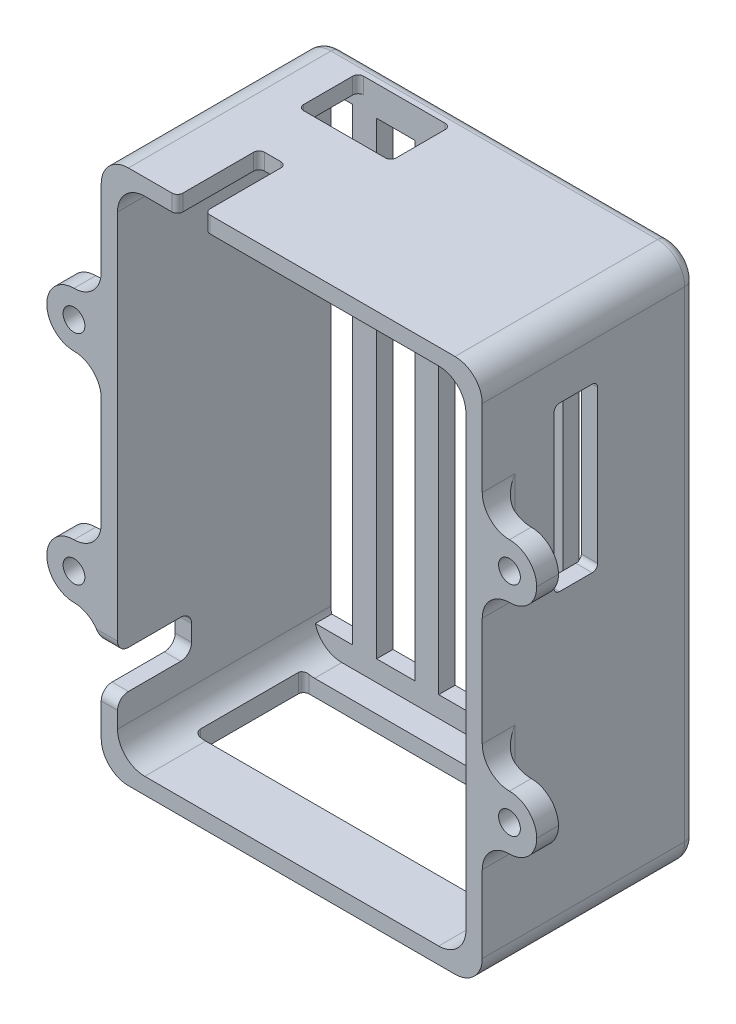
SolidWorks part; units mm, degrees
ref_plane "Front Plane" through (0, 0, 0) normal (0, 0, 1) x (1, 0, 0)
ref_plane "Top Plane" through (0, 0, 0) normal (0, 1, 0) x (1, 0, 0)
ref_plane "Right Plane" through (0, 0, 0) normal (1, 0, 0) x (0, 0, -1)
sketch "Sketch1" plane through (0, 0, 0) normal (0, 0, 1) x (1, 0, 0)
  line L1 (32, -46.145) -> (-32, -46.145)
  line L2 (32, -46.145) -> (32, 46.145)
  line L3 (32, 46.145) -> (-32, 46.145)
  line L4 (-32, -46.145) -> (-32, 46.145)
  line L5 (32, -46.145) -> (-32, 46.145) construction
  line L6 (32, 46.145) -> (-32, -46.145) construction
  line L12 (-25, -42.355) -> (-32, -42.355)
  line L13 (-25, -42.355) -> (-25, 43.645)
  line L14 (-25, 43.645) -> (-32, 43.645)
  line L15 (-32, -42.355) -> (-32, 43.645)
  line L16 (-25, -42.355) -> (-32, 43.645) construction
  line L17 (-25, 43.645) -> (-32, -42.355) construction
  line L57 (-13.6, -42.355) -> (-13.6, 43.645)
  line L58 (-13.6, -42.355) -> (-20.6, -42.355)
  line L59 (-20.6, -42.355) -> (-20.6, 43.645)
  line L60 (-13.6, 43.645) -> (-20.6, 43.645)
  line L61 (-2.2, -42.355) -> (-2.2, 43.645)
  line L62 (-2.2, -42.355) -> (-9.2, -42.355)
  line L63 (-9.2, -42.355) -> (-9.2, 43.645)
  line L64 (-2.2, 43.645) -> (-9.2, 43.645)
  line L65 (9.2, -42.355) -> (9.2, 43.645)
  line L66 (9.2, -42.355) -> (2.2, -42.355)
  line L67 (2.2, -42.355) -> (2.2, 43.645)
  line L68 (9.2, 43.645) -> (2.2, 43.645)
  line L69 (20.6, -42.355) -> (20.6, 43.645)
  line L70 (20.6, -42.355) -> (13.6, -42.355)
  line L71 (13.6, -42.355) -> (13.6, 43.645)
  line L72 (20.6, 43.645) -> (13.6, 43.645)
  line L73 (32, -42.355) -> (32, 43.645)
  line L74 (32, -42.355) -> (25, -42.355)
  line L75 (25, -42.355) -> (25, 43.645)
  line L76 (32, 43.645) -> (25, 43.645)
  line L101 (35, -49.145) -> (-35, -49.145)
  line L102 (35, -49.145) -> (35, 49.145)
  line L103 (35, 49.145) -> (-35, 49.145)
  line L104 (-35, -49.145) -> (-35, 49.145)
  line L105 (35, -49.145) -> (-35, 49.145) construction
  line L106 (35, 49.145) -> (-35, -49.145) construction
  point P0 (0, 0)
  point P7 (0, 0)
  point P8 (-28.5, 0.645)
  dimension "D1" = 64
  dimension "D2" = 86
  dimension "D3" = 2.5
  dimension "D4" = 3
  dimension "D5" = 7
  dimension "D6" = 0
  dimension "D8" = 3
  dimension "D9" = 3
  dimension "D10" = 92.29
  dimension "D7" = 6
extrude "Boss-Extrude1" add sketch "Sketch1" along normal blind 3 contours L4 L1 L2 L3 L65 L66 L58 L12 L15 L14 L13 L62 L70 L73 region at (0, -1.0153, 0)
extrude "Boss-Extrude2" add sketch "Sketch1<3>" along normal blind 39.2 contours L104 L101 L102 L103 L1 L4 L3 L2 region at (0, -47.9383, 0)
sketch "Sketch1<3>" plane through (0, 0, 0) normal (0, 0, 1) x (1, 0, 0) same geometry as "Sketch1"
fillet "Fillet2" radius 5 8 edges at (-32, -46.145, 21.1) (32, -46.145, 21.1) (-32, 46.145, 21.1) (32, 46.145, 21.1) (35, -49.145, 19.6) (-35, -49.145, 19.6) (35, 49.145, 19.6) (-35, 49.145, 19.6)
sketch "Sketch2" plane through (0, 0, 0) normal (0, 1, 0) x (1, 0, 0)
  line L1 (29, -28) -> (-29, -28)
  line L2 (29, -28) -> (29, -8)
  line L3 (29, -8) -> (-29, -8)
  line L4 (-29, -28) -> (-29, -8)
  line L5 (29, -28) -> (-29, -8) construction
  line L6 (29, -8) -> (-29, -28) construction
  line L8 (0, 0) -> (0, -66.913) construction
  point P0 (0, -18)
  dimension "D1" = 28
  dimension "D2" = 20
  dimension "D3" = 58
extrude "Cut-Extrude1" cut sketch "Sketch2" against normal blind 64
fillet "Fillet3" radius 1 4 edges at (-29, -47.4363, 28) (-29, -47.4363, 8) (29, -47.4363, 28) (29, -47.4363, 8)
sketch "Sketch3" plane through (0, 0, 0) normal (1, 0, 0) x (0, 0, -1)
  line L1 (-18, 7.145) -> (-26, 7.145)
  line L2 (-18, 7.145) -> (-18, 37.145)
  line L3 (-18, 37.145) -> (-26, 37.145)
  line L4 (-26, 7.145) -> (-26, 37.145)
  line L5 (-18, 7.145) -> (-26, 37.145) construction
  line L6 (-18, 37.145) -> (-26, 7.145) construction
  line L7 (-39.2, 49.145) -> (0, 49.145) construction
  line L9 (0, -44.145) -> (0, 44.145) construction
  point P0 (-22, 22.145)
  dimension "D1" = 26
  dimension "D2" = 8
  dimension "D3" = 12
  dimension "D4" = 30
extrude "Cut-Extrude2" cut sketch "Sketch3" along normal blind 45
fillet "Fillet4" radius 1 4 edges at (33.5, 7.145, 18) (33.5, 7.145, 26) (33.5, 37.145, 18) (33.5, 37.145, 26)
sketch "Sketch4" plane through (0, 0, 0) normal (0, 1, 0) x (1, 0, 0)
  line L0 (-35, -39.2) -> (-35, 0) construction
  line L1 (-16, -39.2) -> (-21, -39.2)
  line L2 (-16, -39.2) -> (-16, -24.2)
  line L3 (-16, -24.2) -> (-21, -24.2)
  line L4 (-21, -39.2) -> (-21, -24.2)
  line L5 (-16, -39.2) -> (-21, -24.2) construction
  line L6 (-16, -24.2) -> (-21, -39.2) construction
  line L7 (30, -39.2) -> (-30, -39.2) construction
  point P0 (-18.5, -31.7)
  dimension "D1" = 15
  dimension "D2" = 14
  dimension "D3" = 5
extrude "Cut-Extrude3" cut sketch "Sketch4" along normal blind 81
fillet "Fillet5" radius 1 4 edges at (-21, 47.645, 24.2) (-21, 47.645, 39.2) (-16, 47.645, 39.2) (-16, 47.645, 24.2)
ref_plane "Plane1" through (0, 0, 39.2) normal (0, 0, 1) x (1, 0, 0)
sketch "Sketch5" plane through (0, 0, 39.2) normal (0, 0, 1) x (1, 0, 0)
  line L0 (35, -44.145) -> (35, 44.145) construction
  line L1 (35, 15) -> (45, 15)
  line L2 (35, 15) -> (35, 25)
  line L3 (35, 25) -> (45, 25)
  line L4 (45, 15) -> (45, 25)
  line L5 (35, 15) -> (45, 25) construction
  line L6 (35, 25) -> (45, 15) construction
  line L7 (0, 58.3443) -> (0, -58.3443) construction
  line L8 (48.8523, 0) -> (-42.1568, 0) construction
  line L9 (35, -25) -> (45, -15) construction
  line L10 (35, -15) -> (45, -25) construction
  line L11 (45, -15) -> (45, -25)
  line L12 (35, -25) -> (45, -25)
  line L13 (35, -15) -> (35, -25)
  line L14 (35, -15) -> (45, -15)
  line L15 (-35, -15) -> (-45, -25) construction
  line L16 (-35, -25) -> (-45, -15) construction
  line L17 (-35, 25) -> (-45, 15) construction
  line L18 (-35, 15) -> (-45, 25) construction
  line L19 (-35, -15) -> (-45, -15)
  line L20 (-35, -15) -> (-35, -25)
  line L21 (-35, -25) -> (-45, -25)
  line L22 (-45, -15) -> (-45, -25)
  line L23 (-45, 15) -> (-45, 25)
  line L24 (-35, 25) -> (-45, 25)
  line L25 (-35, 15) -> (-35, 25)
  line L26 (-35, 15) -> (-45, 15)
  circle A0 centre (40, 20) radius 2
  circle A1 centre (40, -20) radius 2
  circle A2 centre (-40, 20) radius 2
  circle A3 centre (-40, -20) radius 2
  point P0 (40, 20)
  point P16 (40, -20)
  point P25 (-40, -20)
  point P26 (-40, 20)
  dimension "D4" = 4
  dimension "D5" = 4
  dimension "D6" = 4
  dimension "D7" = 4
  dimension "D1" = 10
  dimension "D2" = 10
  dimension "D3" = 20
extrude "Boss-Extrude3" add sketch "Sketch5" against normal blind 4
fillet "Fillet6" radius 5 8 edges at (35, 25, 37.2) (35, 15, 37.2) (35, -15, 37.2) (35, -25, 37.2) (-35, 25, 37.2) (-35, 15, 37.2) (-35, -15, 37.2) (-35, -25, 37.2)
fillet "Fillet7" radius 5 8 edges at (-45, 25, 37.2) (-45, 15, 37.2) (-45, -15, 37.2) (-45, -25, 37.2) (45, -25, 37.2) (45, -15, 37.2) (45, 15, 37.2) (45, 25, 37.2)
fillet "Fillet8" radius 2 4 edges at (35, -20, 35.2) (35, 20, 35.2) (-35, 20, 35.2) (-35, -20, 35.2)
fillet "Fillet9" radius 2 8 edges at (-33.5355, -47.6805, 0) (0, -49.145, 0) (33.5355, -47.6805, 0) (35, 0, 0) (33.5355, 47.6805, 0) (-33.5355, 47.6805, 0) (0, 49.145, 0) (-35, 0, 0)
sketch "Sketch6" plane through (0, 0, 0) normal (1, 0, 0) x (0, 0, -1)
  line L0 (-39.2, -44.145) -> (-39.2, -30) construction
  line L1 (-39.2, -36.145) -> (-25.6, -36.145)
  line L2 (-39.2, -36.145) -> (-39.2, -29.145)
  line L3 (-39.2, -29.145) -> (-25.6, -29.145)
  line L4 (-25.6, -36.145) -> (-25.6, -29.145)
  line L5 (-39.2, -36.145) -> (-25.6, -29.145) construction
  line L6 (-39.2, -29.145) -> (-25.6, -36.145) construction
  line L7 (-9, -46.145) -> (-27, -46.145) construction
  point P0 (-32.4, -32.645)
  dimension "D1" = 7
  dimension "D2" = 10
  dimension "D3" = 13.6
extrude "Cut-Extrude4" cut sketch "Sketch6" against normal blind 48
fillet "Fillet11" radius 2 4 edges at (-33.5, -36.145, 39.2) (-33.5368, -29.145, 39.2) (-33.5, -36.145, 25.6) (-33.5, -29.145, 25.6)
sketch "Sketch7" plane through (0, 0, 0) normal (0, 1, 0) x (1, 0, 0)
  line L0 (-35, -39.2) -> (-35, -2) construction
  line L1 (-7, -14) -> (-24, -14)
  line L2 (-7, -14) -> (-7, -3)
  line L3 (-7, -3) -> (-24, -3)
  line L4 (-24, -14) -> (-24, -3)
  line L5 (-7, -14) -> (-24, -3) construction
  line L6 (-7, -3) -> (-24, -14) construction
  point P0 (-15.5, -8.5)
  dimension "D1" = 14
  dimension "D2" = 11
  dimension "D3" = 17
  dimension "D4" = 11
extrude "Cut-Extrude5" cut sketch "Sketch7" along normal blind 60
fillet "Fillet12" radius 1 4 edges at (-7, 47.645, 3) (-24, 47.645, 3) (-24, 47.645, 14) (-7, 47.645, 14)
